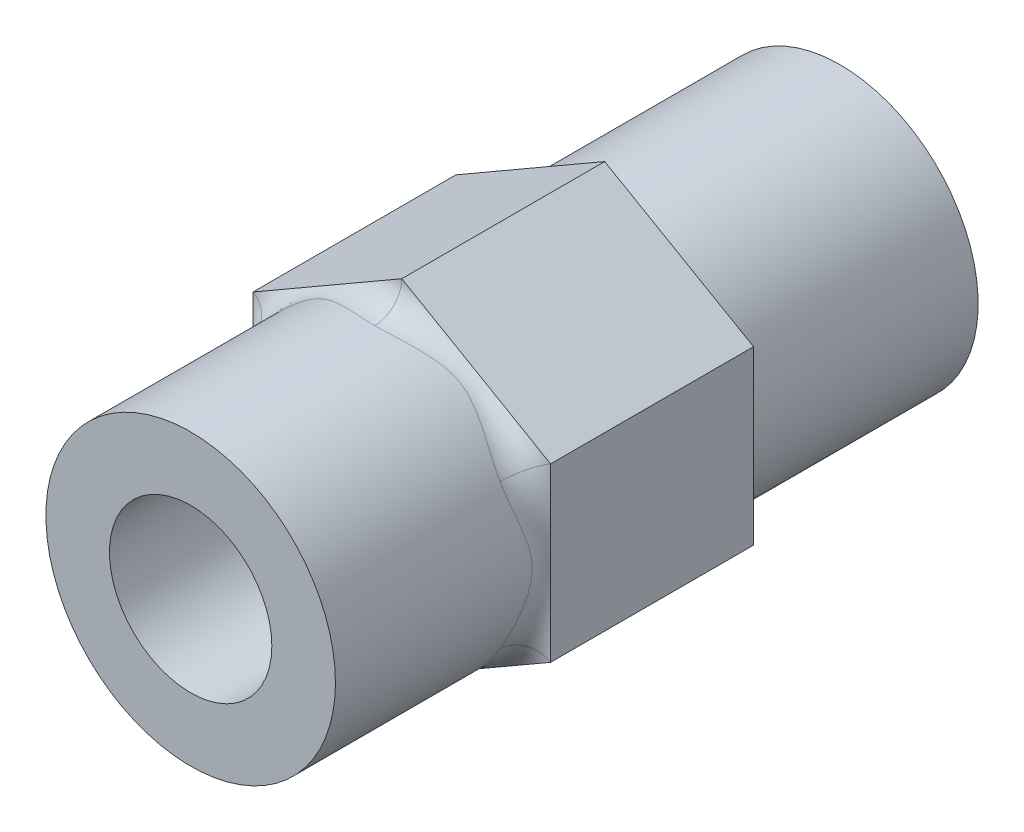
SolidWorks part; units mm, degrees
ref_plane "Front Plane" through (0, 0, 0) normal (0, 0, 1) x (1, 0, 0)
ref_plane "Top Plane" through (0, 0, 0) normal (0, 1, 0) x (1, 0, 0)
ref_plane "Right Plane" through (0, 0, 0) normal (1, 0, 0) x (0, 0, -1)
sketch "Sketch1" plane through (0, 0, 0) normal (0, 0, 1) x (1, 0, 0)
  circle A0 centre (0, 0) radius 5.35
  dimension "D1" = 10.7
extrude "Boss-Extrude1" add sketch "Sketch1" along normal blind 24
sketch "Sketch2" plane through (0, 0, 24) normal (0, 0, 1) x (1, 0, 0)
  circle A0 centre (0, 0) radius 3
  dimension "D1" = 6
extrude "Cut-Extrude1" cut sketch "Sketch2" against normal blind 11.7
sketch "Sketch3" plane through (0, 0, 0) normal (0, 0, -1) x (-1, 0, 0)
  line L0 (0, 0) -> (0, 2.4249) construction
  line L1 (0, 2.4249) -> (-2.1, 1.2124)
  line L2 (-2.1, 1.2124) -> (-2.1, -1.2124)
  line L3 (-2.1, -1.2124) -> (0, -2.4249)
  line L4 (0, -2.4249) -> (2.1, -1.2124)
  line L5 (2.1, -1.2124) -> (2.1, 1.2124)
  line L6 (2.1, 1.2124) -> (0, 2.4249)
  circle A0 centre (0, 0) radius 5.1
  circle A2 centre (0, 0) radius 5.35 construction
  circle A3 centre (0, 0) radius 5.35
  circle A4 centre (0, 0) radius 2.1 construction
  circle M3 centre (0, 0) radius 5.35
  dimension "D1" = 10.2
  dimension "D2" = 4.2
extrude "Cut-Extrude2" cut sketch "Sketch3" against normal up to next contours L5 L6 L1 L2 L3 L4 region at (0, 0, 0)
extrude "Cut-Extrude3" cut sketch "Sketch3<3>" against normal blind 8.7 contours A0 M3 region at (5.1987, 0, 0)
sketch "Sketch3<3>" plane through (0, 0, 0) normal (0, 0, -1) x (-1, 0, 0) same geometry as "Sketch3"
sketch "Sketch4" plane through (0, 0, 8.7) normal (0, 0, -1) x (-1, 0, 0)
  line L0 (0, 0) -> (0, 6.3509) construction
  line L1 (0, 6.3509) -> (-5.5, 3.1754)
  line L2 (-5.5, 3.1754) -> (-5.5, -3.1754)
  line L3 (-5.5, -3.1754) -> (0, -6.3509)
  line L4 (0, -6.3509) -> (5.5, -3.1754)
  line L5 (5.5, -3.1754) -> (5.5, 3.1754)
  line L6 (5.5, 3.1754) -> (0, 6.3509)
  circle A0 centre (0, 0) radius 5.5 construction
  circle A1 centre (0, 0) radius 5.35 construction
  circle A2 centre (0, 0) radius 5.35
  dimension "D1" = 11
extrude "Boss-Extrude2" add sketch "Sketch4" against normal blind 7.5
fillet "Fillet1" radius 1 1 edges at (-5.35, 0, 16.2)
